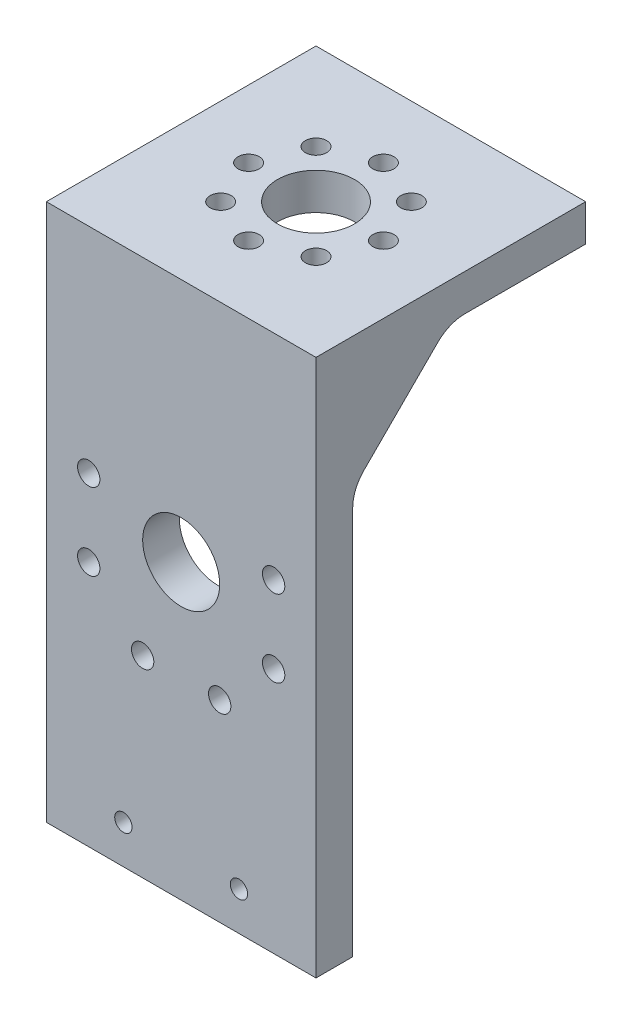
SolidWorks part; units mm, degrees
material "ABS PC"
ref_plane "Front Plane" through (0, 0, 0) normal (0, 0, 1) x (1, 0, 0)
ref_plane "Top Plane" through (0, 0, 0) normal (0, 1, 0) x (1, 0, 0)
ref_plane "Right Plane" through (0, 0, 0) normal (1, 0, 0) x (0, 0, -1)
sketch "Sketch1" plane through (0, 0, 0) normal (0, 1, 0) x (1, 0, 0)
  line L1 (-35, -35) -> (35, -35)
  line L2 (-35, -35) -> (-35, 35)
  line L3 (-35, 35) -> (35, 35)
  line L4 (35, -35) -> (35, 35)
  line L5 (-35, -35) -> (35, 35) construction
  line L6 (-35, 35) -> (35, -35) construction
  point P0 (0, 0)
  dimension "D1" = 70
  dimension "D2" = 70
extrude "Boss-Extrude1" add sketch "Sketch1" along normal blind 9.525 contours L2 L3 L4 L1
sketch "Sketch2" plane through (0, 0, 0) normal (0, -1, 0) x (1, 0, 0)
  circle A0 centre (0, 0) radius 17.5 construction
  circle A1 centre (0, 0) radius 17.5 construction
  circle A2 centre (0, 0) radius 17.5 construction
  circle A3 centre (0, 0) radius 17.5 construction
  circle A4 centre (0, 0) radius 17.5 construction
  circle A5 centre (0, 0) radius 17.5 construction
  circle A6 centre (0, 0) radius 17.5 construction
  circle A7 centre (0, 0) radius 17.5 construction
  point P3 (17.5, 0)
  point P8 (12.3744, -12.3744)
  point P10 (0, -17.5)
  point P12 (-12.3744, -12.3744)
  point P14 (-17.5, 0)
  point P16 (-12.3744, 12.3744)
  point P18 (0, 17.5)
  point P20 (12.3744, 12.3744)
  point P21 (0, 0)
  dimension "D2" = 35
  dimension "D1" = 8
hole_wizard "CBORE for M5 SBHCS1" positions "Sketch3" profile "Sketch4" counterbore size "M5" standard "ANSI Metric" end condition through all
sketch "Sketch3" plane through (0, 0, 0) normal (0, -1, 0) x (-1, 0, 0)
  point P0 (-17.5, 0)
  point P3 (-12.3744, 12.3744)
  point P6 (0, 17.5)
  point P9 (12.3744, 12.3744)
  point P12 (17.5, 0)
  point P15 (12.3744, -12.3744)
  point P18 (0, -17.5)
  point P21 (-12.3744, -12.3744)
sketch "Sketch4" plane through (17.5, 0, 0) normal (1, 0, 0) x (0, 0, -1)
  line L0 (0, 0) -> (0, 9.525)
  line L1 (0, 9.525) -> (2.75, 9.525)
  line L3 (2.75, 9.525) -> (2.75, 2.75)
  line L4 (5.25, 2.75) -> (2.75, 2.75)
  line L5 (5.25, 2.75) -> (5.25, 0.025)
  line L6 (5.25, 0.025) -> (5.275, 0)
  line L7 (5.275, 0) -> (0, 0)
  line L8 (-5.25, 0.025) -> (-5.275, 0) construction
  line L11 (0, -6.35) -> (0, 107.95) construction
  dimension "Thru Hole Dia." = 5.5
  dimension "Thru Hole Depth" = 9.525
  dimension "C'Bore Dia." = 10.5
  dimension "C'Bore Depth" = 2.75
  dimension "Near C'Sink Dia." = 10.55
  dimension "Near C'Sink Angle" = 90
sketch "Sketch5" plane through (0, 0, 0) normal (0, -1, 0) x (1, 0, 0)
  circle A0 centre (0, 0) radius 10
  point P3 (0, 0)
  dimension "D1" = 20
extrude "Cut-Extrude1" cut sketch "Sketch5" against normal through all
sketch "Sketch6" plane through (0, 0, 35) normal (0, 0, 1) x (1, 0, 0)
  line L1 (-35, -130) -> (35, -130)
  line L2 (-35, -130) -> (-35, 0)
  line L3 (-35, 0) -> (35, 0)
  line L4 (35, -130) -> (35, 0)
  line L5 (-35, -130) -> (35, 0) construction
  line L6 (-35, 0) -> (35, -130) construction
  point P0 (0, -65)
  point P6 (0, 0)
  dimension "D1" = 130
extrude "Boss-Extrude2" add sketch "Sketch6" against normal blind 9.525
sketch "Sketch7" plane through (0, 0, 25.475) normal (0, 0, -1) x (-1, 0, 0)
  line L0 (35, -130) -> (-35, -130) construction
  line L1 (0, 38.5) -> (0, -38.5) construction
  circle A0 centre (0, -54) radius 10
  point P2 (10, -80)
  point P3 (24, -66)
  point P4 (24, -46)
  point P7 (0, -130)
  point P8 (0, 0)
  point P11 (-24, -46)
  point P12 (-24, -66)
  point P13 (-10, -80)
  dimension "D1" = 20
  dimension "D2" = 8
  dimension "D3" = 20
  dimension "D4" = 26
  dimension "D5" = 10
  dimension "D6" = 24
  dimension "D7" = 50
hole_wizard "CBORE for M5 SHCS1" positions "Sketch14" profile "Sketch16" counterbore size "M5" standard "ANSI Metric" end condition through all
sketch "Sketch14" plane through (0, 0, 25.475) normal (0, 0, -1) x (-1, 0, 0)
  point P0 (-24, -46)
  point P3 (-24, -66)
  point P6 (-10, -80)
  point P9 (10, -80)
  point P12 (24, -66)
  point P15 (24, -46)
sketch "Sketch16" plane through (24, -46, 25.475) normal (1, 0, 0) x (0, 1, 0)
  line L0 (0, 0) -> (0, 9.525)
  line L1 (0, 9.525) -> (2.9, 9.525)
  line L3 (2.9, 9.525) -> (2.9, 5)
  line L4 (2.9, 5) -> (5, 5)
  line L5 (5, 5) -> (5, 0)
  line L7 (5, 0) -> (0, 0)
  line L11 (0, -6.35) -> (0, 107.95) construction
  dimension "Thru Hole Dia." = 5.8
  dimension "Thru Hole Depth" = 9.525
  dimension "C'Bore Dia." = 10
  dimension "C'Bore Depth" = 5
extrude "Cut-Extrude3" cut sketch "Sketch7" against normal blind 9.525 contours A0
sketch "Sketch17" plane through (-35, 0, 0) normal (-1, 0, 0) x (0, 0, 1)
  line L0 (25.475, 0) -> (25.475, -25)
  line L1 (25.475, 0) -> (25.475, -130) construction
  line L2 (25.475, -25) -> (0.475, 0)
  line L3 (25.475, 0) -> (-35, 0) construction
  line L4 (0.475, 0) -> (25.475, 0)
  dimension "D1" = 25
extrude "Boss-Extrude3" add sketch "Sketch17" against normal blind 8
fillet "Fillet1" radius 10 2 edges at (-31, 0, 0.475) (-31, -25, 25.475)
mirror "Mirror1" about plane through (0, 0, 0) normal (1, 0, 0) of "Fillet1", "Boss-Extrude3"
sketch "Sketch18" plane through (0, 0, 35) normal (0, 0, 1) x (1, 0, 0)
  line L0 (35, -120) -> (-35, -120) construction
  line L1 (35, 9.525) -> (35, -130) construction
  line L2 (-35, 9.525) -> (-35, -130) construction
  line L3 (-35, -130) -> (35, -130) construction
  point P6 (15, -120)
  point P7 (-15, -120)
  point P8 (0, -120)
  dimension "D1" = 30
  dimension "D2" = 15
  dimension "D3" = 10
hole_wizard "M4 Clearance Hole1" positions "Sketch19" profile "Sketch21" hole size "M4" standard "ANSI Metric" end condition through all
sketch "Sketch19" plane through (0, 0, 35) normal (0, 0, 1) x (1, 0, 0)
  point P0 (15, -120)
  point P3 (-15, -120)
sketch "Sketch21" plane through (15, -120, 35) normal (1, 0, 0) x (0, -1, 0)
  line L0 (0, 0) -> (0, 70)
  line L1 (0, 70) -> (2.25, 70)
  line L2 (2.25, 70) -> (2.25, 0)
  line L5 (2.25, 0) -> (0, 0)
  line L11 (0, -6.35) -> (0, 107.95) construction
  dimension "Thru Hole Dia." = 4.5
  dimension "Thru Hole Depth" = 70
